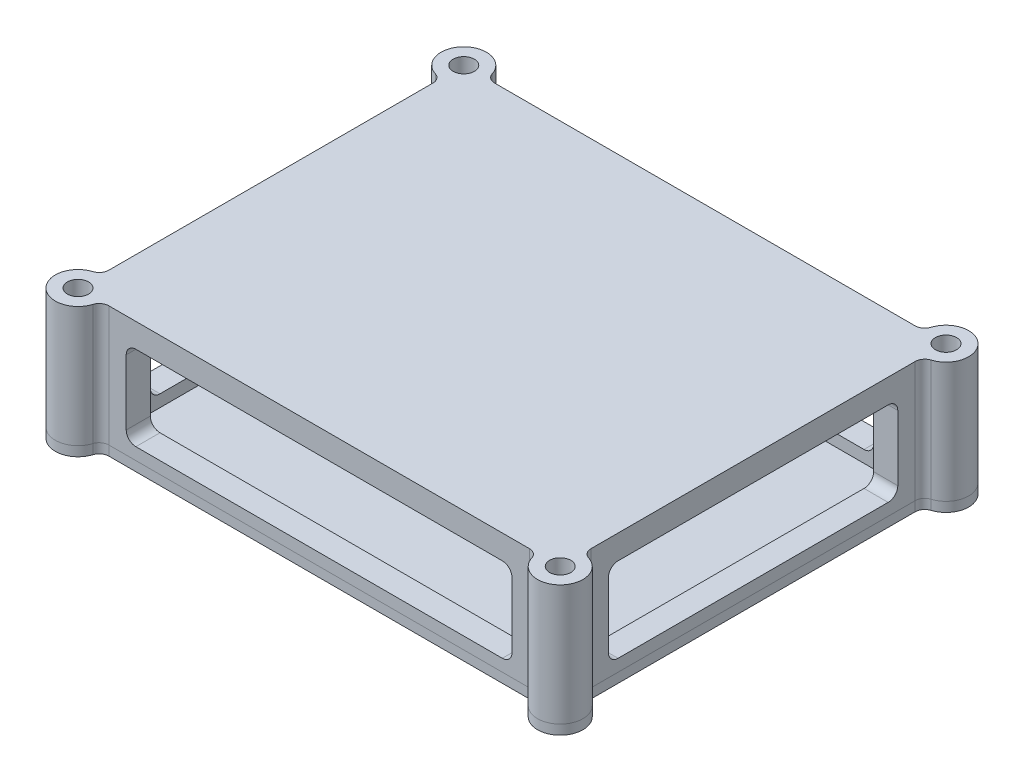
SolidWorks part; units mm, degrees
material "Nylon 101"
ref_plane "Front Plane" through (0, 0, 0) normal (0, 0, 1) x (1, 0, 0)
ref_plane "Top Plane" through (0, 0, 0) normal (0, 1, 0) x (1, 0, 0)
ref_plane "Right Plane" through (0, 0, 0) normal (1, 0, 0) x (0, 0, -1)
sketch "Sketch1" plane through (0, 0, 0) normal (0, 1, 0) x (1, 0, 0)
  line L1 (0, 0) -> (127, 0)
  line L2 (0, 0) -> (0, 101.6)
  line L3 (0, 101.6) -> (127, 101.6)
  line L4 (127, 0) -> (127, 101.6)
  dimension "D1" = 127
  dimension "D2" = 101.6
extrude "Boss-Extrude1" add sketch "Sketch1" along normal blind 31.75
sketch "Sketch3" plane through (0, 0, 0) normal (0, -1, 0) x (1, 0, 0)
  line L1 (6.35, -6.35) -> (120.65, -6.35)
  line L2 (6.35, -6.35) -> (6.35, -95.25)
  line L3 (6.35, -95.25) -> (120.65, -95.25)
  line L4 (120.65, -6.35) -> (120.65, -95.25)
  line L6 (6.35, -50.8) -> (0, -50.8) construction
  line L7 (0, -101.6) -> (0, 0) construction
  line L8 (63.5, -6.35) -> (63.5, 0) construction
  line L9 (0, 0) -> (127, 0) construction
  dimension "D1" = 114.3
  dimension "D2" = 88.9
extrude "Cut-Extrude1" cut sketch "Sketch3" against normal blind 27.94
sketch "Sketch4" plane through (0, 0, -101.6) normal (0, 0, -1) x (-1, 0, 0)
  line L0 (-127, 0) -> (0, 0) construction
  line L1 (-114.3, 25.4) -> (-12.7, 25.4)
  line L2 (-114.3, 25.4) -> (-114.3, 3.175)
  line L3 (-114.3, 3.175) -> (-12.7, 3.175)
  line L4 (-12.7, 25.4) -> (-12.7, 3.175)
  line L5 (-63.5, 25.4) -> (-63.5, 31.75) construction
  line L6 (-127, 31.75) -> (0, 31.75) construction
  dimension "D1" = 22.225
  dimension "D2" = 101.6
  dimension "D3" = 3.175
extrude "Cut-Extrude2" cut sketch "Sketch4" against normal through all
sketch "Sketch5" plane through (127, 0, 0) normal (1, 0, 0) x (0, 0, -1)
  line L1 (12.7, 25.4) -> (88.9, 25.4)
  line L2 (12.7, 25.4) -> (12.7, 3.175)
  line L3 (12.7, 3.175) -> (88.9, 3.175)
  line L4 (88.9, 25.4) -> (88.9, 3.175)
  line L7 (0, 25.4) -> (0, 3.175) construction
  line L8 (50.8, 25.4) -> (50.8, 31.75) construction
  line L9 (0, 31.75) -> (101.6, 31.75) construction
  point P11 (48.7818, 31.75)
  dimension "D2" = 76.2
extrude "Cut-Extrude3" cut sketch "Sketch5" against normal through all contours L2 L1 L4 L3
sketch "Sketch6" plane through (0, 0, 0) normal (0, -1, 0) x (-1, 0, 0)
  line L7 (-127, 101.6) -> (0, 101.6) construction
  line L8 (-127, 101.6) -> (-127, 0) construction
  line L9 (-127, 0) -> (0, 0) construction
  line L10 (0, 101.6) -> (0, 0) construction
  line L19 (-127, 0) -> (-127, 101.6) construction
  circle A0 centre (0, 0) radius 2.794
  circle A1 centre (-127, 0) radius 2.794
  circle A2 centre (0, 101.6) radius 2.794
  circle A3 centre (-127, 101.6) radius 2.794
  circle A8 centre (0, 101.6) radius 5.969
  circle A9 centre (-127, 101.6) radius 5.969
  circle A10 centre (-127, 0) radius 5.969
  circle A11 centre (0, 0) radius 5.969
  line M2 (-127, 101.6) -> (-127, 0)
  line M3 (-127, 0) -> (0, 0)
  line M4 (0, 0) -> (0, 101.6)
  line M40 (0, 101.6) -> (-127, 101.6)
  dimension "D1" = 5.588
  dimension "D2" = 5.588
  dimension "D3" = 5.588
  dimension "D4" = 5.588
  dimension "D6" = 101.6
  dimension "D7" = 3.175
  dimension "D5" = 127
extrude "Boss-Extrude2" add sketch "Sketch6" against normal through all contours A11 A0 M3 M4 | A8 A2 | A9 A3 | A10 A1 M2 M3 region at (-2.095, 0, -2.095) region at (131.1013, 0, -105.7013) region at (131.1013, 0, 4.1013) region at (4.1013, 0, -105.7013)
extrude "Cut-Extrude4" cut sketch "Sketch6<4>" against normal through all contours A2 M40 M4 | A2 M4 M40 | A3 M40 M2 | A3 M2 M40 | A1 M2 M3 | A1 M3 M2 | A0 M3 M4 | A0 M4 M3 region at (-0.3953, 0, 0.3953) region at (1.1858, 0, -1.1858) region at (-0.3953, 0, -101.9953) region at (1.1858, 0, -100.4142) region at (125.8142, 0, -1.1858) region at (127.3953, 0, 0.3953) region at (127.3953, 0, -101.9953) region at (125.8142, 0, -100.4142)
sketch "Sketch6<4>" plane through (0, 0, 0) normal (0, -1, 0) x (-1, 0, 0) same geometry as "Sketch6"
fillet "Fillet1" radius 2.54 24 edges at (0, 15.875, -95.631) (127, 15.875, -5.969) (12.7, 3.175, -3.175) (114.3, 3.175, -3.175) (114.3, 25.4, -3.175) (12.7, 25.4, -3.175) (12.7, 3.175, -98.425) (114.3, 3.175, -98.425) (114.3, 25.4, -98.425) (12.7, 25.4, -98.425) (3.175, 25.4, -88.9) (123.825, 25.4, -12.7) (3.175, 25.4, -12.7) (123.825, 25.4, -88.9) (121.031, 15.875, 0) (5.969, 15.875, 0) (0, 15.875, -5.969) (121.031, 15.875, -101.6) (127, 15.875, -95.631) (5.969, 15.875, -101.6) (3.175, 3.175, -88.9) (3.175, 3.175, -12.7) (123.825, 3.175, -12.7) (123.825, 3.175, -88.9)
sketch "Sketch7" plane through (0, 0, 0) normal (0, -1, 0) x (1, 0, 0)
  line L17 (25.4, -76.2) -> (101.6, -76.2)
  line L19 (25.4, -76.2) -> (101.6, -76.2)
  line L49 (127, -93.4789) -> (127, -8.1211)
  line L50 (8.1211, -101.6) -> (118.8789, -101.6)
  line L51 (0, -8.1211) -> (0, -93.4789)
  line L52 (118.8789, 0) -> (8.1211, 0)
  line L53 (127, -93.4789) -> (127, -8.1211)
  line L54 (8.1211, -101.6) -> (118.8789, -101.6)
  line L55 (0, -8.1211) -> (0, -93.4789)
  line L56 (118.8789, 0) -> (8.1211, 0)
  line L59 (25.4, -25.4) -> (25.4, -76.2)
  line L61 (101.6, -76.2) -> (101.6, -25.4)
  line L62 (101.6, -25.4) -> (25.4, -25.4)
  line L63 (25.4, -25.4) -> (25.4, -76.2)
  line L65 (101.6, -76.2) -> (101.6, -25.4)
  line L66 (101.6, -25.4) -> (25.4, -25.4)
  circle A32 centre (127, 0) radius 2.794 construction
  circle A33 centre (127, 0) radius 2.794
  circle A34 centre (127, -101.6) radius 2.794 construction
  circle A35 centre (127, -101.6) radius 2.794
  circle A36 centre (0, 0) radius 2.794 construction
  circle A37 centre (0, -101.6) radius 2.794 construction
  circle A38 centre (0, 0) radius 2.794
  circle A39 centre (0, -101.6) radius 2.794
  arc A44 (128.7818, -5.6969) -> (121.3031, 1.7818) centre (127, 0) ccw
  arc A45 (128.7818, -5.6969) -> (127, -8.1211) centre (129.54, -8.1211) ccw
  arc A50 (127, -93.4789) -> (128.7818, -95.9031) centre (129.54, -93.4789) ccw
  arc A51 (127, -93.4789) -> (128.7818, -95.9031) centre (129.54, -93.4789) ccw
  arc A52 (0, -8.1211) -> (-1.7818, -5.6969) centre (-2.54, -8.1211) ccw
  arc A53 (5.6969, 1.7818) -> (-1.7818, -5.6969) centre (0, 0) ccw
  arc A54 (5.6969, 1.7818) -> (8.1211, 0) centre (8.1211, 2.54) ccw
  arc A55 (118.8789, 0) -> (121.3031, 1.7818) centre (118.8789, 2.54) ccw
  arc A56 (128.7818, -5.6969) -> (121.3031, 1.7818) centre (127, 0) ccw
  arc A57 (128.7818, -5.6969) -> (127, -8.1211) centre (129.54, -8.1211) ccw
  arc A64 (0, -8.1211) -> (-1.7818, -5.6969) centre (-2.54, -8.1211) ccw
  arc A65 (5.6969, 1.7818) -> (-1.7818, -5.6969) centre (0, 0) ccw
  arc A66 (5.6969, 1.7818) -> (8.1211, 0) centre (8.1211, 2.54) ccw
  arc A67 (118.8789, 0) -> (121.3031, 1.7818) centre (118.8789, 2.54) ccw
  arc A68 (121.3031, -103.3818) -> (128.7818, -95.9031) centre (127, -101.6) ccw
  arc A69 (121.3031, -103.3818) -> (128.7818, -95.9031) centre (127, -101.6) ccw
  arc A70 (121.3031, -103.3818) -> (118.8789, -101.6) centre (118.8789, -104.14) ccw
  arc A71 (121.3031, -103.3818) -> (118.8789, -101.6) centre (118.8789, -104.14) ccw
  arc A72 (8.1211, -101.6) -> (5.6969, -103.3818) centre (8.1211, -104.14) ccw
  arc A74 (-1.7818, -95.9031) -> (5.6969, -103.3818) centre (0, -101.6) ccw
  arc A75 (-1.7818, -95.9031) -> (5.6969, -103.3818) centre (0, -101.6) ccw
  arc A76 (-1.7818, -95.9031) -> (0, -93.4789) centre (-2.54, -93.4789) ccw
  arc A77 (-1.7818, -95.9031) -> (0, -93.4789) centre (-2.54, -93.4789) ccw
  arc A79 (8.1211, -101.6) -> (5.6969, -103.3818) centre (8.1211, -104.14) ccw
  dimension "D1" = 0
  dimension "D2" = 19.05
extrude "Boss-Extrude3" add sketch "Sketch7" along normal blind 2.54 separate body
fillet "Fillet2" radius 2.54 4 edges at (25.4, -1.27, -76.2) (101.6, -1.27, -76.2) (25.4, -1.27, -25.4) (101.6, -1.27, -25.4)
